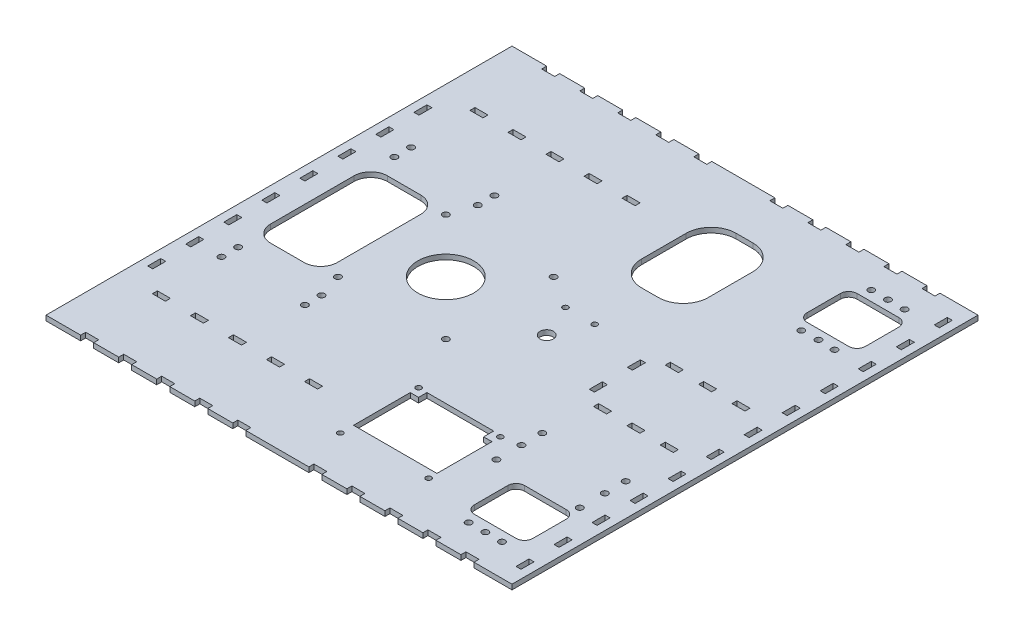
SolidWorks part; units mm, degrees
material "ENPH 253 Hardboard"
ref_plane "Front Plane" through (0, 0, 0) normal (0, 0, 1) x (1, 0, 0)
ref_plane "Top Plane" through (0, 0, 0) normal (0, 1, 0) x (1, 0, 0)
ref_plane "Right Plane" through (0, 0, 0) normal (1, 0, 0) x (0, 0, -1)
sketch "Sketch1" plane through (0, 0, 0) normal (0, 1, 0) x (1, 0, 0)
  line L0 (0, -139.7) -> (0, 139.7) construction
  line L1 (-139.7, 139.7) -> (139.7, 139.7)
  line L2 (-139.7, 139.7) -> (-139.7, -139.7)
  line L3 (-139.7, -139.7) -> (139.7, -139.7)
  line L4 (139.7, 139.7) -> (139.7, -139.7)
  line L5 (-139.7, 139.7) -> (139.7, -139.7) construction
  line L6 (-139.7, -139.7) -> (139.7, 139.7) construction
  line L12 (-139.7, 0) -> (139.7, 0) construction
  point P0 (0, 0)
  dimension "D1" = 279.4
  dimension "D2" = 279.4
extrude "Boss-Extrude1" add sketch "Sketch1" along normal blind 3
sketch "Sketch3" plane through (0, 0, 0) normal (0, -1, 0) x (-1, 0, 0)
  line L0 (-139.7, -139.7) -> (-139.7, 139.7) construction
  line L1 (-134.7, 129.3) -> (-131.7, 129.3)
  line L2 (-134.7, 129.3) -> (-134.7, 121.5)
  line L3 (-134.7, 121.5) -> (-131.7, 121.5)
  line L4 (-131.7, 129.3) -> (-131.7, 121.5)
  line L5 (-139.7, 139.7) -> (139.7, 139.7) construction
  dimension "D1" = 5
  dimension "D2" = 10.4
  dimension "D3" = 7.8
  dimension "D4" = 3
extrude "Cut-Extrude2" cut sketch "Sketch3" against normal through all
pattern_linear "LPattern1" count 12 spacing 22.8 along (0, 0, 1) of "Cut-Extrude2"
sketch "Sketch5" plane through (0, 0, 0) normal (0, -1, 0) x (1, 0, 0)
  line L0 (139.7, -139.7) -> (-139.7, -139.7) construction
  line L1 (109.1, -139.7) -> (116.9, -139.7)
  line L2 (109.1, -139.7) -> (109.1, -136.7)
  line L3 (109.1, -136.7) -> (116.9, -136.7)
  line L4 (116.9, -139.7) -> (116.9, -136.7)
  line L5 (139.7, 139.7) -> (139.7, -139.7) construction
  dimension "D1" = 22.8
  dimension "D2" = 7.8
  dimension "D3" = 3
extrude "Cut-Extrude3" cut sketch "Sketch5" against normal through all
pattern_linear "LPattern2" count 11 spacing 22.8 along (-1, 0, 0) skipping (5, 0) of "Cut-Extrude3"
mirror "Mirror2" about plane through (0, 0, 0) normal (0, 0, 1) of "LPattern2"
sketch "Sketch6" plane through (0, 0, 0) normal (0, -1, 0) x (1, 0, 0)
  line L0 (63.5, -139.7) -> (48.5, -139.7) construction
  line L1 (-134.7, -83.7) -> (-131.7, -83.7)
  line L2 (-134.7, -83.7) -> (-134.7, -75.9)
  line L3 (-134.7, -75.9) -> (-131.7, -75.9)
  line L4 (-131.7, -83.7) -> (-131.7, -75.9)
  line L5 (-139.7, -139.7) -> (-139.7, 139.7) construction
  dimension "D1" = 56
  dimension "D2" = 5
  dimension "D3" = 3
  dimension "D4" = 7.8
extrude "Cut-Extrude4" cut sketch "Sketch6" against normal through all
pattern_linear "LPattern3" count 8 spacing 22.8 along (0, 0, 1) of "Cut-Extrude4"
sketch "Sketch7" plane through (0, 0, 0) normal (0, -1, 0) x (-1, 0, 0)
  line L1 (139.7, 139.7) -> (139.7, -139.7) construction
  line L3 (-63.5, 139.7) -> (-48.5, 139.7) construction
  circle A0 centre (39.7, 0) radius 16.75
  dimension "D1" = 33.5
  dimension "D2" = 100
  dimension "D3" = 139.7
extrude "Cut-Extrude5" cut sketch "Sketch7" against normal through all
hole_wizard "#6 Clearance Hole1" positions "Sketch8" profile "Sketch9" hole size "#6" standard "ANSI Inch" end condition through all
sketch "Sketch8" plane through (0, 3, 0) normal (0, 1, 0) x (1, 0, 0)
  line L0 (-72.025, -32.325) -> (-72.025, 32.325) construction
  line L1 (-72.025, 32.325) -> (-7.375, 32.325) construction
  line L2 (-7.375, 32.325) -> (-7.375, -32.325) construction
  line L3 (-7.375, -32.325) -> (-72.025, -32.325) construction
  point P0 (-72.025, -32.325)
  point P2 (-72.025, 32.325)
  point P4 (-7.375, 32.325)
  point P6 (-7.375, -32.325)
  dimension "D1" = 64.65
  dimension "D2" = 64.65
  dimension "D3" = 90
  dimension "D4" = 64.65
  dimension "D5" = 32.325
  dimension "D6" = 32.325
sketch "Sketch9" plane through (-72.025, 3, 32.325) normal (1, 0, 0) x (0, 0, 1)
  line L0 (0, 0) -> (0, 3)
  line L1 (0, 3) -> (1.8986, 3)
  line L2 (1.8986, 3) -> (1.8986, 0)
  line L5 (1.8986, 0) -> (0, 0)
  line L11 (0, -6.35) -> (0, 107.95) construction
  dimension "Thru Hole Dia." = 3.7973
  dimension "Thru Hole Depth" = 3
hole_wizard "#6 Clearance Hole2" positions "Sketch10" profile "Sketch11" hole size "#6" standard "ANSI Inch" end condition through all
sketch "Sketch10" plane through (0, 3, 0) normal (0, 1, 0) x (1, 0, 0)
  line L1 (-118.9, 139.7) -> (-139.7, 139.7) construction
  line L2 (-139.7, -139.7) -> (-118.9, -139.7) construction
  line L3 (-73.3, 139.7) -> (-88.3, 139.7) construction
  line L4 (-88.3, -139.7) -> (-73.3, -139.7) construction
  line L5 (-139.7, 139.7) -> (-139.7, -139.7) construction
  point P0 (-117.36, 56.83)
  point P2 (-67.36, 56.83)
  point P4 (-117.36, -56.83)
  point P6 (-67.36, -56.83)
  point P22 (-67.36, -46.83)
  point P24 (-117.36, -46.83)
  point P26 (-67.36, 46.83)
  point P28 (-117.36, 46.83)
  dimension "D2" = 50
  dimension "D3" = 22.34
  dimension "D4" = 50
  dimension "D5" = 82.87
  dimension "D6" = 82.87
  dimension "D7" = 82.87
  dimension "D8" = 82.87
  dimension "D9" = 10
  dimension "D10" = 10
  dimension "D11" = 50
  dimension "D12" = 10
  dimension "D13" = 10
  dimension "D14" = 50
  dimension "D15" = 22.34
  dimension "D16" = 22.34
  dimension "D17" = 22.34
sketch "Sketch11" plane through (-117.36, 3, -56.83) normal (1, 0, 0) x (0, 0, 1)
  line L0 (0, 0) -> (0, 3)
  line L1 (0, 3) -> (1.8986, 3)
  line L2 (1.8986, 3) -> (1.8986, 0)
  line L5 (1.8986, 0) -> (0, 0)
  line L11 (0, -6.35) -> (0, 107.95) construction
  dimension "Thru Hole Dia." = 3.7973
  dimension "Thru Hole Depth" = 3
sketch "Sketch14" plane through (0, 0, 0) normal (0, -1, 0) x (-1, 0, 0)
  line L0 (139.7, 139.7) -> (139.7, -139.7) construction
  line L1 (-17.9, 139.7) -> (19.9, 139.7) construction
  circle A0 centre (-20.8, 0) radius 4
  point P6 (-12.05, 20)
  point P7 (-29.55, 20)
  point P8 (0, 0)
  point P9 (0, 0)
  point P10 (0, 0)
  dimension "D1" = 8
  dimension "D2" = 160.5
  dimension "D3" = 139.7
  dimension "D4" = 8.75
  dimension "D5" = 20
  dimension "D6" = 8.75
extrude "Cut-Extrude6" cut sketch "Sketch14" against normal through all
sketch "Sketch16" plane through (0, 0, 0) normal (0, -1, 0) x (1, 0, 0)
  line L0 (-139.7, -139.7) -> (-139.7, 139.7) construction
  line L1 (-118.9, 96.7) -> (-111.1, 96.7)
  line L2 (-118.9, 96.7) -> (-118.9, 93.7)
  line L3 (-118.9, 93.7) -> (-111.1, 93.7)
  line L4 (-111.1, 96.7) -> (-111.1, 93.7)
  line L7 (-111.1, 136.7) -> (-118.9, 136.7) construction
  dimension "D1" = 20.8
  dimension "D2" = 7.8
  dimension "D3" = 40
  dimension "D4" = 3
extrude "Cut-Extrude8" cut sketch "Sketch16" against normal through all
pattern_linear "LPattern5" count 5 spacing 22.8 along (1, 0, 0) of "Cut-Extrude8"
mirror "Mirror4" about plane through (0, 0, 0) normal (0, 0, 1) of "LPattern5"
sketch "Sketch17" plane through (0, 0, 0) normal (0, -1, 0) x (1, 0, 0)
  line L1 (119.7, 23) -> (111.9, 23)
  line L2 (119.7, 23) -> (119.7, 20)
  line L3 (119.7, 20) -> (111.9, 20)
  line L4 (111.9, 23) -> (111.9, 20)
  line L5 (94.1, 139.7) -> (109.1, 139.7) construction
  line L6 (139.7, 139.7) -> (139.7, -139.7) construction
  point P8 (119.7, 21.5)
  dimension "D1" = 116.7
  dimension "D2" = 20
  dimension "D3" = 7.8
  dimension "D4" = 3
extrude "Cut-Extrude9" cut sketch "Sketch17" against normal through all
pattern_linear "LPattern6" count 3 spacing 20 along (-1, 0, 0) of "Cut-Extrude9"
sketch "Sketch18" plane through (0, 0, 0) normal (0, -1, 0) x (-1, 0, 0)
  line L0 (-139.7, -139.7) -> (-139.7, 139.7) construction
  line L1 (-64.7, -15.3) -> (-61.7, -15.3)
  line L2 (-64.7, -15.3) -> (-64.7, -7.5)
  line L3 (-64.7, -7.5) -> (-61.7, -7.5)
  line L4 (-61.7, -15.3) -> (-61.7, -7.5)
  line L5 (-71.3, -139.7) -> (-86.3, -139.7) construction
  dimension "D1" = 7.8
  dimension "D2" = 3
  dimension "D3" = 75
  dimension "D4" = 124.4
extrude "Cut-Extrude10" cut sketch "Sketch18" against normal through all
mirror "Mirror5" about plane through (0, 0, 0) normal (0, 0, 1) of "Cut-Extrude10", "LPattern6", "Cut-Extrude9"
sketch "Sketch19" plane through (0, 0, 0) normal (0, -1, 0) x (1, 0, 0)
  line L0 (0, 0) -> (139.7, 0) construction
  line L1 (24.7, -109.7) -> (34.7, -109.7)
  line L2 (9.7, -94.7) -> (9.7, -68)
  line L3 (24.7, -53) -> (34.7, -53)
  line L4 (49.7, -94.7) -> (49.7, -68)
  line L9 (139.7, 139.7) -> (139.7, -139.7) construction
  line L10 (86.3, -139.7) -> (71.3, -139.7) construction
  line L11 (79.7, -23) -> (71.9, -23) construction
  line L16 (-139.7, -139.7) -> (-139.7, 139.7) construction
  line L17 (-89.7, 35) -> (-109.7, 35)
  line L18 (-79.7, 25) -> (-79.7, -25)
  line L19 (-89.7, -35) -> (-109.7, -35)
  line L20 (-119.7, 25) -> (-119.7, -25)
  line L21 (9.7, 104.7) -> (59.7, 104.7)
  line L22 (9.7, 65.7) -> (59.7, 65.7) construction
  line L23 (9.7, 65.7) -> (9.7, 109.7) construction
  line L24 (9.7, 109.7) -> (59.7, 109.7) construction
  line L25 (59.7, 65.7) -> (59.7, 109.7) construction
  line L29 (14.7, 65.7) -> (54.7, 65.7)
  line L30 (25.7, 139.7) -> (40.7, 139.7) construction
  line L32 (59.7, 104.7) -> (59.7, 71.7) construction
  line L34 (9.7, 104.7) -> (9.7, 70.7) construction
  line L35 (139.7, 139.7) -> (139.7, -139.7) construction
  line L38 (9.7, 104.7) -> (9.7, 70.7)
  line L39 (9.7, 70.7) -> (14.7, 70.7)
  line L40 (14.7, 70.7) -> (14.7, 65.7)
  line L41 (54.7, 65.7) -> (54.7, 71.7)
  line L42 (54.7, 71.7) -> (59.7, 71.7)
  line L43 (59.7, 71.7) -> (59.7, 104.7)
  arc A1 (34.7, -53) -> (49.7, -68) centre (34.7, -68) cw
  arc A2 (34.7, -109.7) -> (49.7, -94.7) centre (34.7, -94.7) ccw
  arc A3 (24.7, -109.7) -> (9.7, -94.7) centre (24.7, -94.7) cw
  arc A4 (9.7, -68) -> (24.7, -53) centre (24.7, -68) cw
  circle A9 centre (-39.7, 0) radius 16.75 construction
  arc A10 (-79.7, -25) -> (-89.7, -35) centre (-89.7, -25) cw
  arc A11 (-89.7, 35) -> (-79.7, 25) centre (-89.7, 25) cw
  arc A12 (-109.7, 35) -> (-119.7, 25) centre (-109.7, 25) ccw
  arc A13 (-109.7, -35) -> (-119.7, -25) centre (-109.7, -25) cw
  point P25 (14.5222, 70.5222)
  point P43 (-79.7, -35)
  point P46 (-79.7, 35)
  dimension "D9" = 35
  dimension "D10" = 10
  dimension "D11" = 44
  dimension "D12" = 50
  dimension "D1" = 15
  dimension "D2" = 30
  dimension "D3" = 90
  dimension "D4" = 30
  dimension "D5" = 40
  dimension "D6" = 70
  dimension "D7" = 20
  dimension "D8" = 40
  dimension "D13" = 5
  dimension "D15" = 5
  dimension "D17" = 30
  dimension "D18" = 80
  dimension "D14" = 6
extrude "Cut-Extrude11" cut sketch "Sketch19" against normal through all
hole_wizard "#4 Clearance Hole1" positions "Sketch20" profile "Sketch21" hole size "#4" standard "ANSI Inch" end condition through all
sketch "Sketch20" plane through (0, 3, 0) normal (0, 1, 0) x (1, 0, 0)
  line L0 (9.7, -104.7) -> (9.7, -70.7) construction
  line L1 (59.7, -71.7) -> (59.7, -104.7) construction
  point P0 (9.7, -65.7)
  point P2 (59.7, -66.7)
  point P4 (59.7, -109.7)
  point P6 (9.7, -112.7)
  dimension "D1" = 5
  dimension "D2" = 8
  dimension "D3" = 5
  dimension "D4" = 1
sketch "Sketch21" plane through (9.7, 3, 65.7) normal (1, 0, 0) x (0, 0, 1)
  line L0 (0, 0) -> (0, 3)
  line L1 (0, 3) -> (1.6319, 3)
  line L2 (1.6319, 3) -> (1.6319, 0)
  line L5 (1.6319, 0) -> (0, 0)
  line L11 (0, -6.35) -> (0, 107.95) construction
  dimension "Thru Hole Dia." = 3.2639
  dimension "Thru Hole Depth" = 3
sketch "Sketch22" plane through (0, 3, 0) normal (0, 1, 0) x (1, 0, 0)
  line L5 (92.2, -84.7) -> (117.2, -84.7)
  line L6 (87.2, -89.7) -> (87.2, -109.7)
  line L7 (92.2, -114.7) -> (117.2, -114.7)
  line L8 (122.2, -89.7) -> (122.2, -109.7)
  line L9 (139.7, -139.7) -> (139.7, 139.7) construction
  line L10 (94.1, -139.7) -> (109.1, -139.7) construction
  line L11 (139.7, 0) -> (94.1968, 0) construction
  line L12 (92.2, 114.7) -> (117.2, 114.7)
  line L13 (122.2, 89.7) -> (122.2, 109.7)
  line L14 (92.2, 84.7) -> (117.2, 84.7)
  line L15 (87.2, 89.7) -> (87.2, 109.7)
  arc A0 (87.2, -109.7) -> (92.2, -114.7) centre (92.2, -109.7) ccw
  arc A1 (92.2, -84.7) -> (87.2, -89.7) centre (92.2, -89.7) ccw
  arc A2 (117.2, -84.7) -> (122.2, -89.7) centre (117.2, -89.7) cw
  arc A3 (117.2, -114.7) -> (122.2, -109.7) centre (117.2, -109.7) ccw
  arc A4 (92.2, 84.7) -> (87.2, 89.7) centre (92.2, 89.7) cw
  arc A5 (122.2, 89.7) -> (117.2, 84.7) centre (117.2, 89.7) cw
  arc A6 (117.2, 114.7) -> (122.2, 109.7) centre (117.2, 109.7) cw
  arc A7 (92.2, 114.7) -> (87.2, 109.7) centre (92.2, 109.7) ccw
  point P2 (87.2, -114.7)
  point P9 (87.2, -84.7)
  point P23 (122.2, -84.7)
  point P26 (122.2, -114.7)
  point P29 (87.2, 84.7)
  point P32 (122.2, 84.7)
  point P35 (122.2, 114.7)
  point P38 (87.2, 114.7)
  dimension "D1" = 5
  dimension "D5" = 17.5
  dimension "D6" = 35
  dimension "D7" = 25
  dimension "D8" = 30
extrude "Cut-Extrude12" cut sketch "Sketch22" against normal up to next contours L8 L5 L6 L7 | L15 L14 L13 L12 region at (104.7, 3, 99.7) region at (104.7, 3, -99.7)
hole_wizard "#6 Clearance Hole3" positions "Sketch25" profile "Sketch26" hole size "#6" standard "ANSI Inch" end condition through all
sketch "Sketch25" plane through (0, 3, 0) normal (0, 1, 0) x (1, 0, 0)
  line L0 (70.35, -52.2) -> (70.35, -79.7) construction
  line L2 (70.35, -79.7) -> (120.35, -79.7) construction
  line L3 (120.35, -79.7) -> (120.35, -52.2) construction
  line L4 (120.35, -52.2) -> (70.35, -52.2) construction
  line L6 (70.35, -64.7) -> (120.35, -64.7) construction
  line L8 (92.2, -84.7) -> (117.2, -84.7) construction
  line L9 (104.7, 79.0309) -> (104.7, 120.7) construction
  line L10 (104.7, 120.7) -> (94.7, 120.7) construction
  line L11 (94.7, 120.7) -> (94.7, 78.7) construction
  line L12 (94.7, 78.7) -> (114.7, 78.7) construction
  line L13 (114.7, 78.7) -> (114.7, 120.7) construction
  line L14 (114.7, 120.7) -> (94.7, 120.7) construction
  line L16 (92.2, 84.7) -> (117.2, 84.7) construction
  line L17 (92.2, 114.7) -> (117.2, 114.7) construction
  line L18 (0, 0) -> (139.7, 0) construction
  line L19 (139.7, -139.7) -> (139.7, 139.7) construction
  point P0 (94.7, 120.7)
  point P2 (114.7, 120.7)
  point P4 (114.7, 78.7)
  point P6 (94.7, 78.7)
  point P8 (104.7, 79.0309)
  point P10 (104.7, 120.7)
  point P12 (70.35, -52.2)
  point P14 (70.35, -79.7)
  point P16 (70.35, -64.7)
  point P18 (120.35, -64.7)
  point P20 (120.35, -52.2)
  point P22 (120.35, -79.7)
  point P43 (104.7, -84.7)
  point P56 (104.7, 84.7)
  point P59 (161.7487, 56.9763)
  point P68 (114.7, -120.7)
  point P69 (104.7, -120.7)
  point P70 (94.7, -120.7)
  dimension "D1" = 27.5
  dimension "D2" = 5
  dimension "D3" = 15
  dimension "D4" = 50
  dimension "D5" = 15.65
  dimension "D6" = 20
  dimension "D7" = 10
  dimension "D8" = 6
  dimension "D9" = 6
sketch "Sketch26" plane through (94.7, 3, -120.7) normal (1, 0, 0) x (0, 0, 1)
  line L0 (0, 0) -> (0, 3)
  line L1 (0, 3) -> (1.8986, 3)
  line L2 (1.8986, 3) -> (1.8986, 0)
  line L5 (1.8986, 0) -> (0, 0)
  line L11 (0, -6.35) -> (0, 107.95) construction
  dimension "Thru Hole Dia." = 3.7973
  dimension "Thru Hole Depth" = 3
hole_wizard "#4 Clearance Hole2" positions "Sketch27" profile "Sketch28" hole size "#4" standard "ANSI Inch" end condition up to next
sketch "Sketch27" plane through (0, 3, 0) normal (0, 1, 0) x (1, 0, 0)
  point P0 (12.05, 20)
  point P2 (29.55, 20)
  point P6 (0, 0)
  point P7 (0, 0)
sketch "Sketch28" plane through (12.05, 3, -20) normal (1, 0, 0) x (0, 0, 1)
  line L0 (0, 0) -> (0, 3)
  line L1 (0, 3) -> (1.6319, 3)
  line L2 (1.6319, 3) -> (1.6319, 0)
  line L5 (1.6319, 0) -> (0, 0)
  line L11 (0, -6.35) -> (0, 107.95) construction
  dimension "Thru Hole Dia." = 3.2639
  dimension "Thru Hole Depth" = 3
equation "\"45mmm\"=50"
